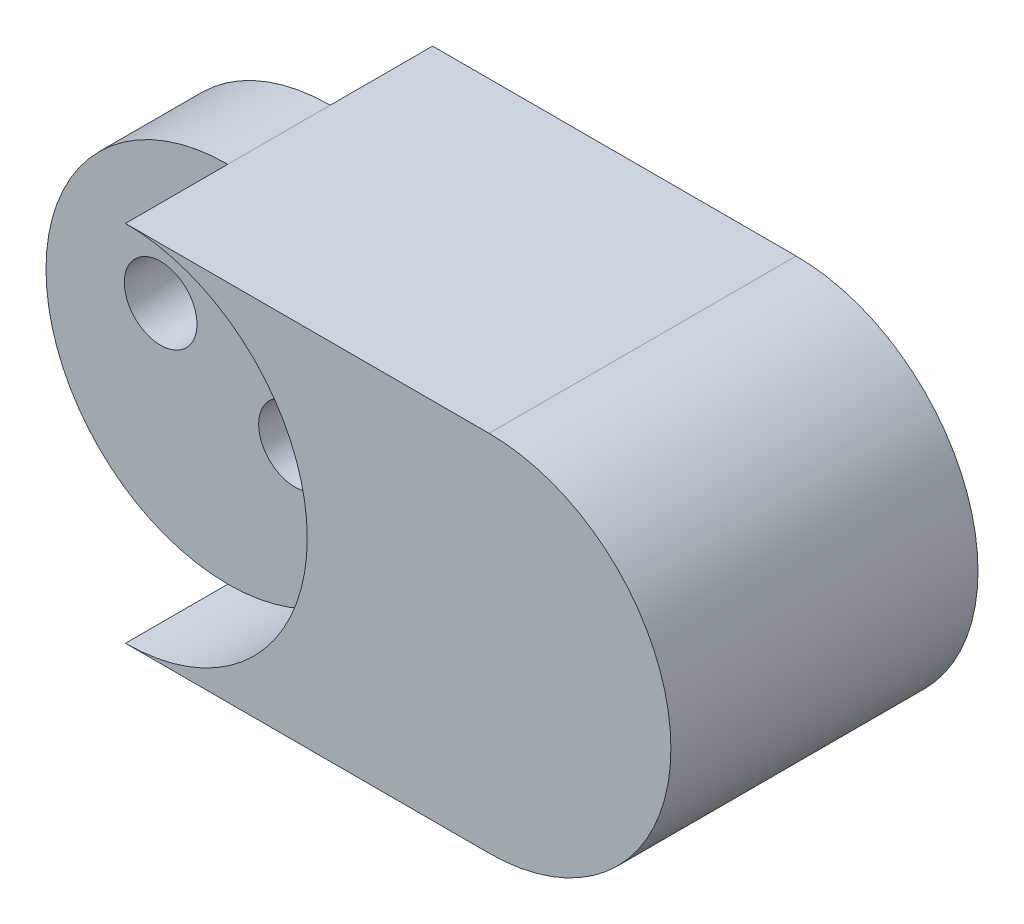
SolidWorks part; units mm, degrees
ref_plane "Front Plane" through (0, 0, 0) normal (0, 0, 1) x (1, 0, 0)
ref_plane "Top Plane" through (0, 0, 0) normal (0, 1, 0) x (1, 0, 0)
ref_plane "Right Plane" through (0, 0, 0) normal (1, 0, 0) x (0, 0, -1)
sketch "Sketch1" plane through (0, 0, 0) normal (0, 0, 1) x (1, 0, 0)
  line L0 (0, 0) -> (-3.2798, 1.3585) construction
  line L1 (0, 0) -> (-0.8875, 0) construction
  line L2 (-1.6399, 0.6793) -> (7.2401, 0.6793) construction
  line L3 (-1.6399, 5.1193) -> (7.2401, 5.1193)
  line L4 (-1.6399, -3.7607) -> (7.2401, -3.7607)
  circle A0 centre (0, 0) radius 0.8875
  circle A2 centre (-3.2798, 1.3585) radius 0.8875
  arc A4 (-1.6399, 5.1193) -> (-1.6399, -3.7607) centre (-1.6399, 0.6793) ccw
  arc A5 (7.2401, -3.7607) -> (7.2401, 5.1193) centre (7.2401, 0.6793) ccw
  point P8 (2.8001, 0.6793)
  dimension "D1" = 1.775
  dimension "D2" = 4.44
  dimension "D3" = 3.55
  dimension "D4" = 22.5
  dimension "D5" = 8.88
extrude "Boss-Extrude1" add sketch "Sketch1" along normal blind 7.5
sketch "Sketch2" plane through (0, 0, 0) normal (0, 0, -1) x (-1, 0, 0)
  circle A0 centre (1.6399, 0.6793) radius 4.44
  arc A1 (1.6399, -3.7607) -> (1.6399, 5.1193) centre (1.6399, 0.6793) ccw construction
extrude "Cut-Extrude1" cut sketch "Sketch2" against normal blind 2.5
extrude "Cut-Extrude2" cut sketch "Sketch2<2>" against normal blind 2.5 from offset 5 offset against normal yes
sketch "Sketch2<2>" plane through (0, 0, 0) normal (0, 0, -1) x (-1, 0, 0) same geometry as "Sketch2"
equation "\"filamentDi\"=1.775"
equation "\"D1@Sketch1\"=\"filamentDi\""
